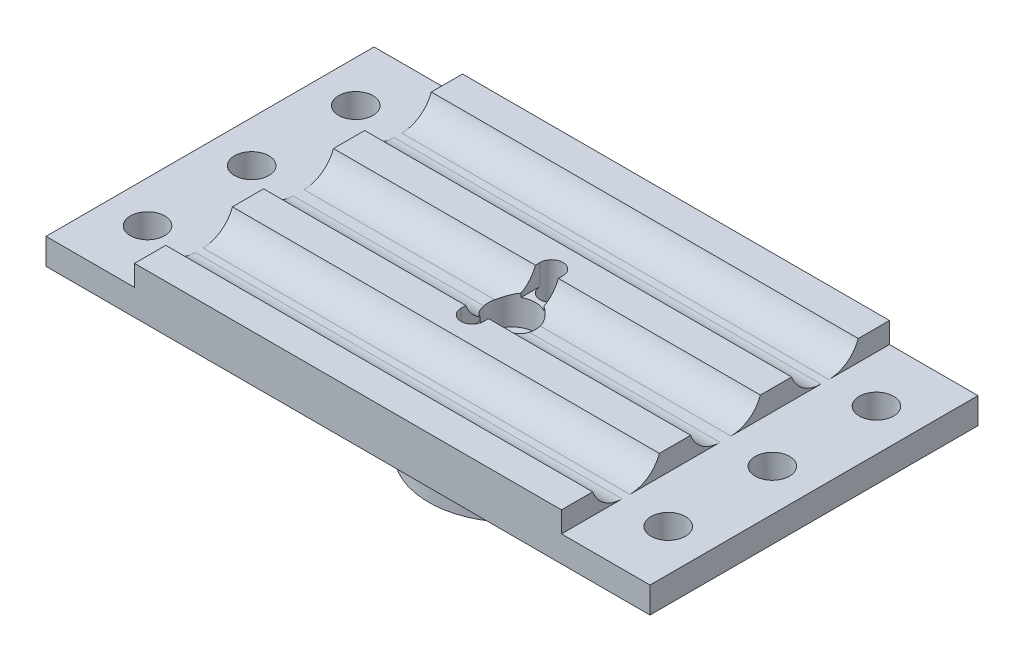
SolidWorks part; units mm, degrees
material "PETG"
ref_plane "Спереди" through (0, 0, 0) normal (0, 0, 1) x (1, 0, 0)
ref_plane "Сверху" through (0, 0, 0) normal (0, 1, 0) x (1, 0, 0)
ref_plane "Справа" through (0, 0, 0) normal (1, 0, 0) x (0, 0, -1)
sketch "Эскиз1" plane through (0, 0, 0) normal (0, 1, 0) x (1, 0, 0)
  circle A0 centre (0, 0) radius 50
  dimension "D1" = 100
extrude "Бобышка-Вытянуть1" add sketch "Эскиз1" along normal blind 2.5
sketch "Эскиз2" plane through (0, 0, 0) normal (0, -1, 0) x (1, 0, 0)
  circle A0 centre (0, 0) radius 8
  dimension "D1" = 16
extrude "Бобышка-Вытянуть2" add sketch "Эскиз2" along normal blind 9
sketch "Эскиз3" plane through (0, -9, 0) normal (0, -1, 0) x (1, 0, 0)
  circle A0 centre (0, 0) radius 6.1
  dimension "D1" = 12.2
extrude "Вырез-Вытянуть1" cut sketch "Эскиз3" against normal blind 2
sketch "Эскиз4" plane through (0, -7, 0) normal (0, -1, 0) x (1, 0, 0)
  line L0 (0, 0) -> (50000, 0) construction
  line L13 (0, 0) -> (0, 50000) construction
  line L14 (-3.1, 5.2536) -> (-3.1, -5.2536)
  line L15 (3.1, 5.2536) -> (3.1, -5.2536)
  circle A17 centre (0, 0) radius 6.1 construction
  arc A18 (-3.1, -5.2536) -> (3.1, -5.2536) centre (0, 0) ccw
  circle A19 centre (0, 0) radius 6.1 construction
  arc A20 (3.1, 5.2536) -> (-3.1, 5.2536) centre (0, 0) ccw
  dimension "D1" = 6.2
extrude "Вырез-Вытянуть2" cut sketch "Эскиз4" against normal blind 5
sketch "Эскиз7" plane through (0, 2.5, 0) normal (0, 1, 0) x (1, 0, 0)
  circle A0 centre (0, 0) radius 1.15
  dimension "D1" = 2.3
extrude "Вырез-Вытянуть4" cut sketch "Эскиз7" against normal up to surface (4.5 mm away) up to face at (0, -2, 0)
sketch "Эскиз8" plane through (0, 2.5, 0) normal (0, 1, 0) x (1, 0, 0)
  circle A0 centre (0, 0) radius 2.25
  dimension "D1" = 4.5
extrude "Вырез-Вытянуть5" cut sketch "Эскиз8" against normal blind 2.5
sketch "Эскиз11" plane through (0, 0, 0) normal (0, -1, 0) x (1, 0, 0)
  line L0 (0, 0) -> (-50000, 0) construction
  line L1 (0, 0) -> (0, 50000) construction
  circle A0 centre (0, 3.8) radius 1.1
  circle A1 centre (0, -3.8) radius 1.1
  dimension "D2" = 2.2
  dimension "D1" = 7.6
extrude "Вырез-Вытянуть6" cut sketch "Эскиз11" along normal through all both and the other way through all
sketch "Эскиз14" plane through (0, 2.5, 0) normal (0, 1, 0) x (1, 0, 0)
  line L0 (0, 0) -> (-50000, 0) construction
  line L1 (0, 0) -> (0, 50000) construction
  line L2 (-25, 10) -> (-25, 0) construction
  circle A0 centre (-25, 0) radius 1.65
  circle A1 centre (-25, 10) radius 1.65
  circle A2 centre (-25, -10) radius 1.65
  circle A3 centre (25, -10) radius 1.65
  circle A4 centre (25, 0) radius 1.65
  circle A5 centre (25, 10) radius 1.65
  dimension "D1" = 3.3
  dimension "D2" = 10
  dimension "D3" = 25
extrude "Вырез-Вытянуть7" cut sketch "Эскиз14" against normal up to surface (2.5 mm away) up to face at (0, 0, -8)
sketch "Эскиз15" plane through (0, 2.5, 0) normal (0, 1, 0) x (1, 0, 0)
  line L1 (29, 15.75) -> (-29, 15.75)
  line L2 (29, 15.75) -> (29, -15.75)
  line L3 (29, -15.75) -> (-29, -15.75)
  line L4 (-29, 15.75) -> (-29, -15.75)
  line L5 (29, 15.75) -> (-29, -15.75) construction
  line L6 (29, -15.75) -> (-29, 15.75) construction
  circle A0 centre (0, 0) radius 50 construction
  circle A1 centre (0, 0) radius 50
  point P0 (0, 0)
  dimension "D1" = 58
  dimension "D2" = 31.5
extrude "Вырез-Вытянуть8" cut sketch "Эскиз15" against normal up to surface (2.5 mm away) up to face at (-25, 0, -8.35)
sketch "Эскиз16" plane through (0, 2.5, 0) normal (0, 1, 0) x (1, 0, 0)
  line L0 (-20.5, 15.75) -> (-20.5, -15.75) construction
  line L1 (29, 15.75) -> (-29, 15.75) construction
  line L2 (-29, -15.75) -> (29, -15.75) construction
  line L3 (0, 0) -> (0, 50000) construction
  line L4 (20.5, 15.75) -> (20.5, -15.75) construction
  line L5 (-29, 15.75) -> (-29, -15.75) construction
  line L6 (0, 0) -> (-50000, 0) construction
  line L7 (-20.5, 15.75) -> (20.5, 15.75)
  line L8 (20.5, 15.75) -> (20.5, 12.75)
  line L9 (20.5, 12.75) -> (-20.5, 12.75)
  line L10 (-20.5, 12.75) -> (-20.5, 15.75)
  line L11 (-20.5, 6.35) -> (20.5, 6.35)
  line L12 (20.5, 6.35) -> (20.5, 3.35)
  line L13 (20.5, 3.35) -> (-20.5, 3.35)
  line L14 (-20.5, 3.35) -> (-20.5, 6.35)
  line L15 (20.5, -3.35) -> (-20.5, -3.35)
  line L16 (20.5, -6.35) -> (20.5, -3.35)
  line L17 (-20.5, -6.35) -> (20.5, -6.35)
  line L18 (-20.5, -3.35) -> (-20.5, -6.35)
  line L19 (20.5, -12.75) -> (-20.5, -12.75)
  line L20 (20.5, -15.75) -> (20.5, -12.75)
  line L21 (-20.5, -15.75) -> (20.5, -15.75)
  line L22 (-20.5, -12.75) -> (-20.5, -15.75)
  circle A0 centre (0, 3.8) radius 1.1 construction
  dimension "D4" = 7.85
  dimension "D5" = 1.45
  dimension "D1" = 8.5
  dimension "D2" = 3
  dimension "D3" = 6.4
extrude "Бобышка-Вытянуть4" add sketch "Эскиз16" along normal blind 2
sketch "Эскиз17" plane through (0, 2.5, 0) normal (0, 1, 0) x (1, 0, 0)
  line L0 (-1.1, 3.8) -> (-1.1, 2.7)
  line L1 (-1.1, 2.7) -> (1.1, 2.7)
  line L2 (1.1, 2.7) -> (1.1, 3.8)
  line L3 (-1.1, -3.8) -> (-1.1, -2.7)
  line L4 (-1.1, -2.7) -> (1.1, -2.7)
  line L5 (1.1, -2.7) -> (1.1, -3.8)
  circle A0 centre (0, 3.8) radius 1.1 construction
  circle A1 centre (0, -3.8) radius 1.1 construction
  arc A2 (1.1, 3.8) -> (-1.1, 3.8) centre (0, 3.8) ccw
  arc A3 (-1.1, -3.8) -> (1.1, -3.8) centre (0, -3.8) ccw
extrude "Вырез-Вытянуть9" cut sketch "Эскиз17" along normal up to surface (2 mm away) up to face at (0, 4.5, 4.85)
fillet "Скругление3" radius 3 8 edges at (0, 2.5, 12.75) (0, 2.5, 6.35) (10.8, 2.5, 3.35) (-10.8, 2.5, 3.35) (-10.8, 2.5, -3.35) (10.8, 2.5, -3.35) (0, 2.5, -6.35) (0, 2.5, -12.75)
